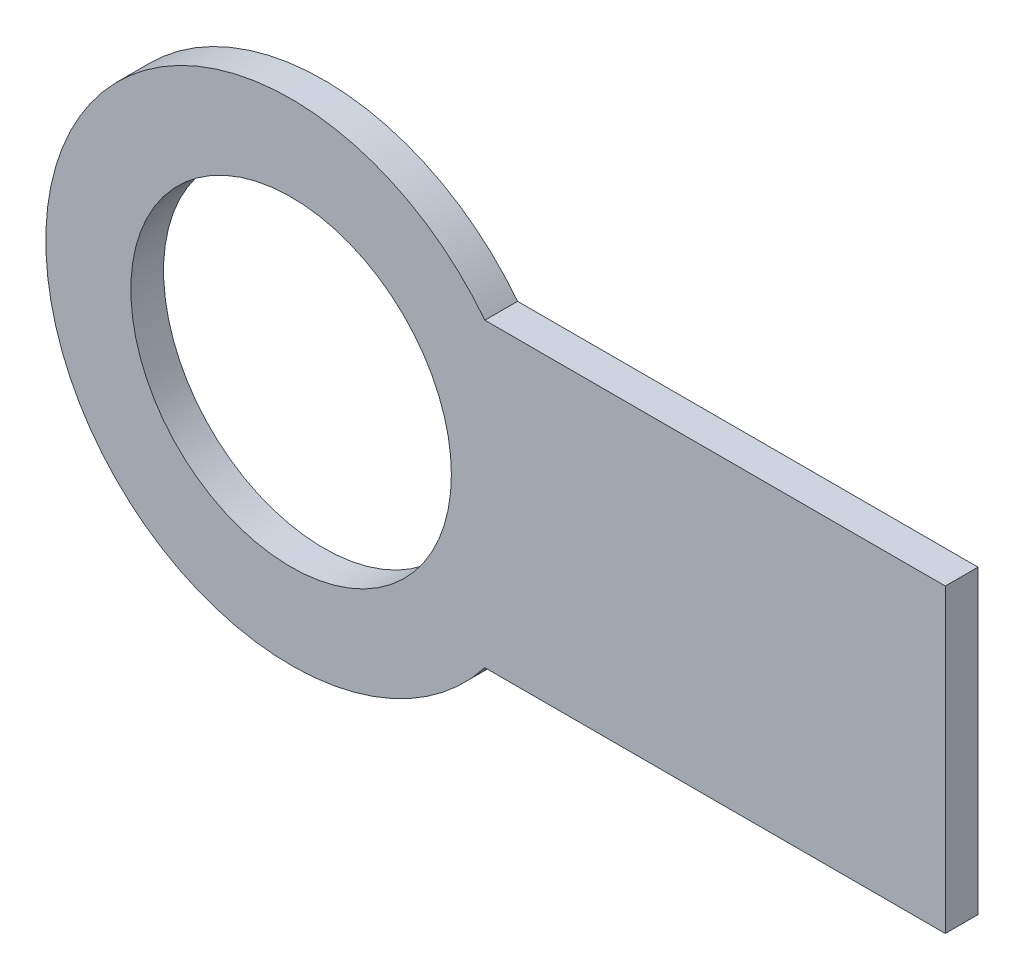
SolidWorks part; units mm, degrees
ref_plane "Top" through (0, 0, 0) normal (0, 0, 1) x (1, 0, 0)
ref_plane "Front" through (0, 0, 0) normal (0, 1, 0) x (1, 0, 0)
ref_plane "Right" through (0, 0, 0) normal (1, 0, 0) x (0, 0, -1)
sketch "Body Sketch" plane through (0, 0, 0) normal (0, 0, 1) x (1, 0, 0)
  line L0 (2.9618, 2.3) -> (10, 2.3)
  line L1 (10, 2.3) -> (10, -2.3)
  line L2 (2.9618, -2.3) -> (10, -2.3)
  line L3 (0, 0) -> (10, 0) construction
  line L4 (-3.75, 2.3) -> (-3.75, -2.3) construction
  circle A0 centre (0, 0) radius 2.45
  arc A1 (2.9618, 2.3) -> (2.9618, -2.3) centre (0, 0) ccw
  dimension "D1" = 4.6
  dimension "D2" = 7.5
  dimension "D3" = 4.9
  dimension "D4" = 13.75
base flange "Base-Flange1" sketch "Body Sketch" thickness 0.5 reverse thickness direction no parameters "D1"=0.7366
sketch "Bend-Lines1" [suppressed] plane through (0, 0, 0) normal (0, 1, 0) x (-1, 0, 0)
sketch "Bounding-Box1" [suppressed] plane through (0, 0, 0) normal (0, 1, 0) x (-1, 0, 0)
sheet metal parameters "Sheet-Metal1" thickness 0.5 parameters "D1"=0.7366
flat pattern "Flat-Pattern1" [suppressed]
sketch "Bend-Lines2" plane through (0, 0, 0) normal (0, 1, 0) x (-1, 0, 0)
sketch3d "Bounding-Box2" [suppressed]
  line L0 (3.75, -3.75, 0) -> (-10, -3.75, 0) construction
  line L1 (3.75, 3.75, 0) -> (-10, 3.75, 0) construction
  line L2 (3.75, -3.75, 0) -> (3.75, 3.75, 0) construction
  line L3 (-10, -3.75, 0) -> (-10, 3.75, 0) construction
